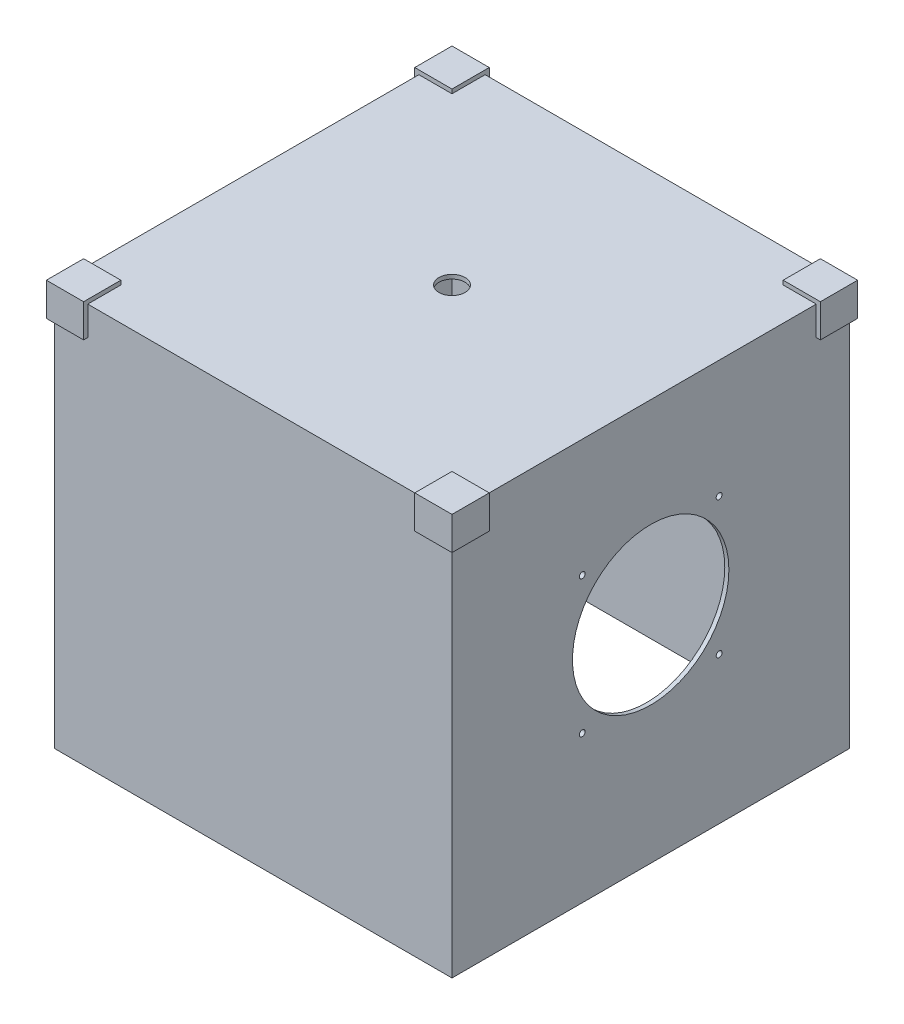
SolidWorks part; units mm, degrees
material "Glass"
ref_plane "Front Plane" through (0, 0, 0) normal (0, 0, 1) x (1, 0, 0)
ref_plane "Top Plane" through (0, 0, 0) normal (0, 1, 0) x (1, 0, 0)
ref_plane "Right Plane" through (0, 0, 0) normal (1, 0, 0) x (0, 0, -1)
sketch "Sketch1" plane through (0, 0, 0) normal (0, 1, 0) x (1, 0, 0)
  line L1 (-152.4, -152.4) -> (152.4, -152.4)
  line L2 (-152.4, -152.4) -> (-152.4, 152.4)
  line L3 (-152.4, 152.4) -> (152.4, 152.4)
  line L4 (152.4, -152.4) -> (152.4, 152.4)
  line L5 (-152.4, -152.4) -> (152.4, 152.4) construction
  line L6 (-152.4, 152.4) -> (152.4, -152.4) construction
  line L7 (149.225, -149.225) -> (-149.225, -149.225)
  line L8 (149.225, -149.225) -> (149.225, 149.225)
  line L9 (149.225, 149.225) -> (-149.225, 149.225)
  line L10 (-149.225, -149.225) -> (-149.225, 149.225)
  line L11 (149.225, -149.225) -> (-149.225, 149.225) construction
  line L12 (149.225, 149.225) -> (-149.225, -149.225) construction
  circle A0 centre (0, 0) radius 10
  point P0 (0, 0)
  point P6 (0, 0)
  dimension "D5" = 20
  dimension "D1" = 304.8
  dimension "D2" = 304.8
  dimension "D3" = 3.175
  dimension "D4" = 3.175
extrude "Boss-Extrude1" add sketch "Sketch1" against normal blind 3.175 contours L10 L7 L8 L9 A0 | L1 L4 L3 L2 L7 L10 L9 L8 region at (-151.9689, 0, 0) region at (0, 0, 145.0043)
extrude "Boss-Extrude2" add sketch "Sketch1<3>" against normal blind 307.975 contours L1 L4 L3 L2 L7 L10 L9 L8 region at (-151.9689, 0, 0)
sketch "Sketch1<3>" plane through (0, 0, 0) normal (0, 1, 0) x (1, 0, 0) same geometry as "Sketch1"
sketch "Sketch3" plane through (0, 0, 0) normal (0, 1, 0) x (1, 0, 0)
  line L1 (-152.4, 152.4) -> (-127, 152.4)
  line L2 (-152.4, 152.4) -> (-152.4, 127)
  line L3 (-152.4, 127) -> (-127, 127)
  line L4 (-127, 152.4) -> (-127, 127)
  line L5 (-127, 152.4) -> (-152.4, 152.4)
  line L6 (-127, 152.4) -> (-127, 155.575)
  line L7 (-127, 155.575) -> (-155.575, 155.575)
  line L10 (-155.575, 155.575) -> (-155.575, 127)
  line L11 (-155.575, 127) -> (-152.4, 127)
  line L12 (-152.4, 152.4) -> (-152.4, 127)
  dimension "D1" = 3.175
  dimension "D2" = 3.175
  dimension "D3" = 25.4
  dimension "D4" = 25.4
extrude "Boss-Extrude3" add sketch "Sketch3" along normal blind 3.175 contours L4 L3 region at (-139.7, 0, -139.7)
extrude "Boss-Extrude4" add sketch "Sketch3<3>" along normal blind 3.175 and the other way blind 22.225 contours L10 L11 L6 L7 region at (-152.8041, 0, -139.7)
sketch "Sketch3<3>" plane through (0, 0, 0) normal (0, 1, 0) x (1, 0, 0) same geometry as "Sketch3"
ref_axis "Axis1" through (0, 0, 0) along (0, 1, 0)
pattern_circular "CirPattern1" count 4 over 360 about axis through (0, 0, 0) along (0, 1, 0) of "Boss-Extrude3", "Boss-Extrude4"
sketch "Sketch5" plane through (0, -307.975, 0) normal (0, -1, 0) x (1, 0, 0)
  line L0 (-149.225, 123.825) -> (-146.05, 123.825)
  line L1 (-146.05, 123.825) -> (-146.05, 146.05)
  line L2 (-146.05, 146.05) -> (-123.825, 146.05)
  line L3 (-123.825, 146.05) -> (-123.825, 149.225)
  line L4 (-123.825, 149.225) -> (-149.225, 149.225)
  line L5 (-149.225, 149.225) -> (-149.225, 123.825)
  line L6 (149.225, 149.225) -> (-149.225, 149.225) construction
  line L7 (-149.225, 149.225) -> (-149.225, -149.225) construction
  point P2 (-145.2377, 145.5403)
  point P10 (-149.225, 149.225)
  dimension "D1" = 3.175
  dimension "D2" = 3.175
  dimension "D3" = 25.4
  dimension "D4" = 25.4
extrude "Boss-Extrude5" add sketch "Sketch5" against normal blind 25.4
pattern_circular "CirPattern2" count 4 over 360 about axis through (0, 0, 0) along (0, 1, 0) of "Boss-Extrude5"
sketch "Sketch6" plane through (149.225, 0, 0) normal (-1, 0, 0) x (0, 0, 1)
  line L0 (163.6826, -142.875) -> (493.0111, -142.875) construction
  line L2 (0, 0) -> (0, 71.1464) construction
  line L6 (149.225, -3.175) -> (149.225, -282.575) construction
  line L7 (149.225, -3.175) -> (149.225, -282.575) construction
  line L10 (52.5, -195.375) -> (-52.5, -195.375) construction
  line L11 (52.5, -195.375) -> (52.5, -90.375) construction
  line L12 (52.5, -90.375) -> (-52.5, -90.375) construction
  line L13 (-52.5, -195.375) -> (-52.5, -90.375) construction
  line L14 (52.5, -195.375) -> (-52.5, -90.375) construction
  line L15 (52.5, -90.375) -> (-52.5, -195.375) construction
  circle A0 centre (0, -142.875) radius 60
  circle A1 centre (-52.5, -90.375) radius 2.25
  circle A2 centre (52.5, -90.375) radius 2.25
  circle A3 centre (52.5, -195.375) radius 2.25
  circle A4 centre (-52.5, -195.375) radius 2.25
  point P3 (0, -142.875)
  point P9 (149.225, -142.875)
  dimension "D1" = 120
  dimension "D2" = 4.5
  dimension "D3" = 105
extrude "Cut-Extrude1" cut sketch "Sketch6" against normal through all both and the other way through all
